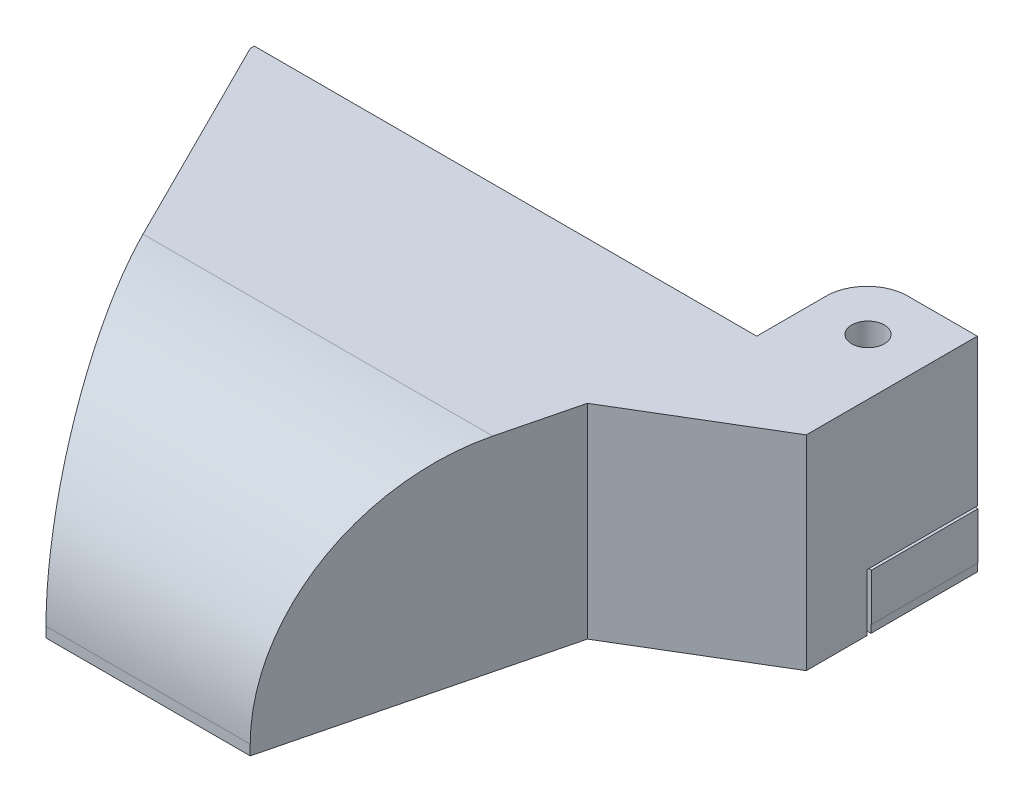
SolidWorks part; units mm, degrees
ref_plane "前视基准面" through (0, 0, 0) normal (0, 0, 1) x (1, 0, 0)
ref_plane "上视基准面" through (0, 0, 0) normal (0, 1, 0) x (1, 0, 0)
ref_plane "右视基准面" through (0, 0, 0) normal (1, 0, 0) x (0, 0, -1)
other "Configuration Table"
sketch "草图1" plane through (0, 0, 0) normal (0, 1, 0) x (1, 0, 0)
  line L1 (0, 0) -> (30, 0)
  line L2 (0, 0) -> (0, -6)
  line L3 (0, -6) -> (30, -6)
  line L4 (30, 0) -> (30, -6)
  dimension "D1" = 30
  dimension "D2" = 6
extrude "凸台-拉伸1" add sketch "草图1" along normal blind 2
sketch "草图2" plane through (0, 2, 0) normal (0, 1, 0) x (1, 0, 0)
  line L0 (30, -6) -> (30, 0) construction
  line L1 (30, 0) -> (0, 0) construction
  circle A0 centre (27.25, -3) radius 0.8
  dimension "D2" = 1.6
  dimension "D3" = 3
  dimension "D1" = 2.75
extrude "切除-拉伸1" cut sketch "草图2" against normal blind 2
sketch "草图3" plane through (0, 2, 0) normal (0, 1, 0) x (1, 0, 0)
  line L0 (0, 0) -> (0, -6) construction
  line L1 (0, -5.8) -> (1.6, -5.8)
  line L2 (0, -5.8) -> (0, -6)
  line L3 (0, -6) -> (1.6, -6)
  line L4 (1.6, -5.8) -> (1.6, -6)
  line L5 (0, -6) -> (30, -6) construction
  line L6 (30, 0) -> (0, 0) construction
  line L7 (30, -6) -> (30, 0) construction
  line L8 (23.4, -6) -> (25, -6)
  line L9 (23.4, -6) -> (23.4, -5.8)
  line L10 (23.4, -5.8) -> (25, -5.8)
  line L11 (25, -6) -> (25, -5.8)
  dimension "D1" = 1.6
  dimension "D2" = 5.8
  dimension "D3" = 5.8
  dimension "D4" = 1.6
  dimension "D5" = 5
extrude "凸台-拉伸2" add sketch "草图3" along normal blind 10
sketch "草图4" plane through (0, 12, 0) normal (0, 1, 0) x (1, 0, 0)
  line L1 (1.6, -5.8) -> (23.4, -5.8)
  line L2 (1.6, -5.8) -> (1.6, -6)
  line L3 (1.6, -6) -> (23.4, -6)
  line L4 (23.4, -5.8) -> (23.4, -6)
extrude "凸台-拉伸3" add sketch "草图4" against normal blind 1.6
sketch "草图5" plane through (0, 2, 0) normal (0, 1, 0) x (1, 0, 0)
  line L1 (25, -5.8) -> (30, -5.8)
  line L2 (25, -5.8) -> (25, -6)
  line L3 (25, -6) -> (30, -6)
  line L4 (30, -5.8) -> (30, -6)
extrude "凸台-拉伸4" add sketch "草图5" along normal blind 10
sketch "草图6" plane through (0, 0, 5.8) normal (0, 0, -1) x (-1, 0, 0)
  line L1 (-30, 12) -> (-24.6, 12)
  line L2 (-30, 12) -> (-30, 4.8)
  line L3 (-30, 4.8) -> (-24.6, 4.8)
  line L4 (-24.6, 12) -> (-24.6, 4.8)
  dimension "D1" = 5.4
  dimension "D2" = 7.2
extrude "凸台-拉伸5" add sketch "草图6" along normal blind 5.4
fillet "圆角1" radius 2 1 edges at (24.6, 8.4, 0.4)
sketch "草图7" plane through (0, 4.8, 0) normal (0, -1, 0) x (-1, 0, 0)
  circle A0 centre (-27.25, -3) radius 0.8
  dimension "D1" = 1.6
extrude "切除-拉伸2" cut sketch "草图7" against normal through all
sketch "草图8" plane through (0, 0, 0) normal (-1, 0, 0) x (0, 0, 1)
  line L1 (0, 2) -> (6, 2)
  line L2 (0, 2) -> (0, 0)
  line L3 (0, 0) -> (6, 0)
  line L4 (6, 2) -> (6, 0)
extrude "切除-拉伸3" cut sketch "草图8" against normal through all
sketch "草图9" plane through (0, 0, 6) normal (0, 0, 1) x (1, 0, 0)
  line L0 (23.4, 10.4) -> (23.4, 2) construction
  line L1 (1.6, 2) -> (23.4, 2)
  line L2 (1.6, 2) -> (1.6, 3.6)
  line L3 (1.6, 3.6) -> (23.4, 3.6)
  line L4 (23.4, 2) -> (23.4, 3.6)
  dimension "D1" = 1.6
extrude "凸台-拉伸7" add sketch "草图9" against normal up to surface (0.2 mm away) up to face at (15.92, 6.24, 5.8)
ref_plane "分割" through (0, 0, 6) normal (0, 0, 1) x (1, 0, 0)
sketch "草图11" plane through (0, 2, 0) normal (0, -1, 0) x (-1, 0, 0)
  line L0 (0, -6) -> (-10, -26)
  line L1 (-10, -26) -> (-20, -26)
  line L2 (-20, -26) -> (-25, -6)
  line L3 (0, -6) -> (-30, -6) construction
  line L4 (-25, -6) -> (0, -6)
  point P7 (-15, -26)
  dimension "D3" = 20
  dimension "D1" = 1.6
  dimension "D4" = 10
  dimension "D2" = 15
extrude "凸台-拉伸9" add sketch "草图11" against normal blind 1.6
sketch "草图12" plane through (0, 3.6, 0) normal (0, 1, 0) x (1, 0, 0)
  line L11 (2.5889, -7.6) -> (10.9889, -24.4)
  line L12 (10.9889, -24.4) -> (18.7508, -24.4)
  line L13 (18.7508, -24.4) -> (22.9508, -7.6)
  line L16 (23.4, -5.8) -> (1.6, -5.8)
  line L17 (1.6, -5.8) -> (1.6, -6)
  line L18 (1.6, -6) -> (0, -6)
  line L19 (0, -6) -> (10, -26)
  line L20 (10, -26) -> (20, -26)
  line L21 (20, -26) -> (25, -6)
  line L22 (25, -6) -> (23.4, -6)
  line L23 (23.4, -6) -> (23.4, -5.8)
  line L26 (1.6, -6) -> (0, -6)
  line L27 (0, -6) -> (10, -26)
  line L28 (10, -26) -> (20, -26)
  line L29 (20, -26) -> (25, -6)
  line L30 (25, -6) -> (23.4, -6)
  line L32 (2.5889, -7.6) -> (1.6, -6)
  line L33 (22.9508, -7.6) -> (23.4, -6)
  line L35 (21.8, -7.4) -> (3.2, -7.4) construction
  line L36 (21.8, -7.6) -> (21.8, -7.4) construction
  line L37 (22.9508, -7.6) -> (21.8, -7.6) construction
  line L38 (23.4, -5.8) -> (1.6, -5.8) construction
  line L39 (23.4, -6) -> (23.4, -5.8) construction
  line L40 (3.2, -7.6) -> (2.5889, -7.6) construction
  line L41 (3.2, -7.4) -> (3.2, -7.6) construction
  line L42 (1.6, -5.8) -> (1.6, -6) construction
  dimension "D1" = 0
  dimension "D2" = 1.6
extrude "凸台-拉伸10" add sketch "草图12" along normal up to surface (8.4 mm away) up to face at (27.25, 12, 2.2)
sketch "草图13" plane through (0, 12, 0) normal (0, 1, 0) x (1, 0, 0)
  line L16 (1.6, -5.8) -> (1.6, -6)
  line L17 (1.6, -6) -> (2.5889, -7.6)
  line L18 (2.5889, -7.6) -> (10.9889, -24.4)
  line L19 (10.9889, -24.4) -> (18.7508, -24.4)
  line L20 (18.7508, -24.4) -> (22.9508, -7.6)
  line L21 (22.9508, -7.6) -> (23.4, -6)
  line L22 (23.4, -6) -> (23.4, -5.8)
  line L23 (23.4, -5.8) -> (1.6, -5.8)
  line L24 (1.6, -5.8) -> (1.6, -6)
  line L25 (1.6, -6) -> (2.5889, -7.6)
  line L26 (2.5889, -7.6) -> (10.9889, -24.4)
  line L27 (10.9889, -24.4) -> (18.7508, -24.4)
  line L28 (18.7508, -24.4) -> (22.9508, -7.6)
  line L29 (22.9508, -7.6) -> (23.4, -6)
  line L30 (23.4, -6) -> (23.4, -5.8)
  line L31 (23.4, -5.8) -> (1.6, -5.8)
  dimension "D1" = 0
extrude "凸台-拉伸11" add sketch "草图13" against normal blind 1.6
sketch "草图15" plane through (0, 2, 0) normal (0, -1, 0) x (1, 0, 0)
  line L0 (10.9889, 24.4) -> (18.7508, 24.4)
  line L1 (18.7508, 24.4) -> (19.7508, 20.4)
  line L2 (19.7508, 20.4) -> (8.9889, 20.4)
  line L3 (8.9889, 20.4) -> (10.9889, 24.4)
  line L4 (20, 26) -> (10, 26) construction
  line L5 (10, 26) -> (0, 6) construction
  line L6 (25, 6) -> (20, 26) construction
  dimension "D1" = 1.6
  dimension "D2" = 180
  dimension "D3" = 180
  dimension "D4" = 1.6
  dimension "D5" = 1.6
  dimension "D6" = 4
extrude "切除-拉伸4" cut sketch "草图15" against normal blind 1.6
fillet "圆角2" radius 9 1 edges at (14.8698, 10.4, 24.4)
fillet "圆角3" radius 9.5 1 edges at (15, 12, 26)
fillet "圆角4" radius 1 1 edges at (14.3698, 3.6, 20.4)
chamfer "倒角1" distance 7 angle 45 1 edges at (25, 7, 6) first distance on face at (22.3766, 6.4935, 16.4935)
sketch "草图16" plane through (0, 2, 0) normal (0, -1, 0) x (-1, 0, 0)
  line L1 (-24.7346, -5.6086) -> (-30, -5.6086)
  line L2 (-24.7346, -5.6086) -> (-24.7346, -0.4)
  line L3 (-24.7346, -0.4) -> (-30, -0.4)
  line L4 (-30, -5.6086) -> (-30, -0.4)
extrude "凸台-拉伸12" add sketch "草图16" against normal blind 0.4 separate body
sketch "草图17" plane through (0, 2.4, 0) normal (0, 1, 0) x (1, 0, 0)
  line L0 (30, -5.6086) -> (24.7346, -5.6086) construction
  line L1 (24.7346, -0.4) -> (25.5346, -0.4)
  line L2 (24.7346, -0.4) -> (24.7346, -5.6086)
  line L3 (24.7346, -5.6086) -> (25.5346, -5.6086)
  line L4 (25.5346, -0.4) -> (25.5346, -5.6086)
  line L5 (26.2346, -0.4) -> (26.2346, -5.6086)
  line L6 (26.2346, -0.4) -> (27.0346, -0.4)
  line L7 (27.0346, -0.4) -> (27.0346, -5.6086)
  line L8 (26.2346, -5.6086) -> (27.0346, -5.6086)
  line L9 (27.7346, -0.4) -> (27.7346, -5.6086)
  line L10 (27.7346, -0.4) -> (28.5346, -0.4)
  line L11 (28.5346, -0.4) -> (28.5346, -5.6086)
  line L12 (27.7346, -5.6086) -> (28.5346, -5.6086)
  line L13 (29.2346, -0.4) -> (29.2346, -5.6086)
  line L14 (29.2346, -0.4) -> (30.0346, -0.4)
  line L15 (30.0346, -0.4) -> (30.0346, -5.6086)
  line L16 (29.2346, -5.6086) -> (30.0346, -5.6086)
  dimension "D1" = 0.8
  dimension "D2" = 4
extrude "凸台-拉伸13" add sketch "草图17" along normal blind 2.3
equation "\"D2@草图11\"=\"D1@草图1\"/2"
